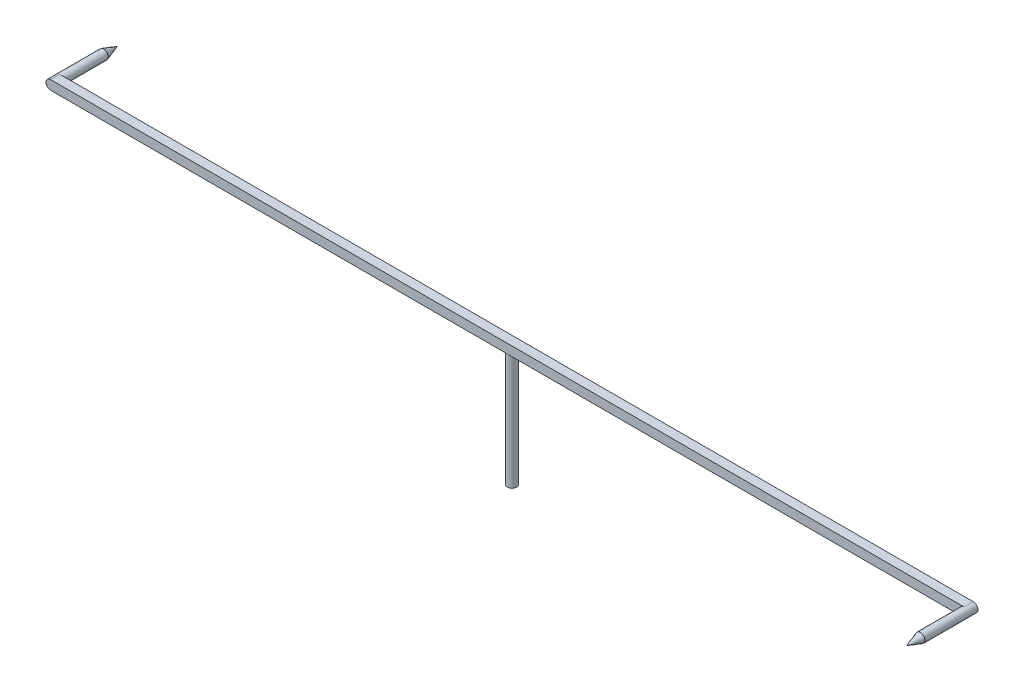
SolidWorks part; units mm, degrees
ref_plane "前视基准面" through (0, 0, 0) normal (0, 0, 1) x (1, 0, 0)
ref_plane "上视基准面" through (0, 0, 0) normal (0, 1, 0) x (1, 0, 0)
ref_plane "右视基准面" through (0, 0, 0) normal (1, 0, 0) x (0, 0, -1)
sketch "草图1" plane through (0, 0, 0) normal (0, 1, 0) x (1, 0, 0)
  circle A0 centre (0, 0) radius 0.4
  dimension "D1" = 0.8
extrude "凸台-拉伸1" add sketch "草图1" along normal blind 10
sketch "草图2" plane through (0, 10, 0) normal (0, 1, 0) x (1, 0, 0)
  line L1 (-40, 0.4) -> (40, 0.4)
  line L2 (-40, 0.4) -> (-40, -0.4)
  line L3 (-40, -0.4) -> (40, -0.4)
  line L4 (40, 0.4) -> (40, -0.4)
  circle A0 centre (0, 0) radius 0.4 construction
  dimension "D1" = 40
  dimension "D2" = 40
extrude "凸台-拉伸2" add sketch "草图2" along normal blind 0.8
fillet "圆角1" radius 0.4 4 edges at (40, 10, 0) (40, 10.8, 0) (-40, 10, 0) (-40, 10.8, 0)
sketch "草图3" plane through (0, 0, 0.4) normal (0, 0, 1) x (1, 0, 0)
  circle A0 centre (39.6, 10.4) radius 0.4
  dimension "D1" = 0.8
extrude "凸台-拉伸3" add sketch "草图3" along normal blind 3.8
sketch "草图4" plane through (0, 0, -0.4) normal (0, 0, -1) x (-1, 0, 0)
  circle A0 centre (39.6, 10.4) radius 0.4
  dimension "D1" = 0.8
extrude "凸台-拉伸4" add sketch "草图4" along normal blind 3.8
ref_plane "基准面1" through (0, 10.4, 0) normal (0, 1, 0) x (1, 0, 0)
sketch "草图5" plane through (0, 10.4, 0) normal (0, 1, 0) x (1, 0, 0)
  line L0 (39.6, -4.2) -> (39.6, -5.4)
  line L1 (39.2, -4.2) -> (40, -4.2) construction
  line L2 (40, -4.2) -> (39.6, -5.4)
  line L3 (39.6, -4.2) -> (40, -4.2)
  dimension "D1" = 1.2
revolve "旋转1" add sketch "草图5" angle 360 about L0
sketch "草图6" plane through (0, 10.4, 0) normal (0, 1, 0) x (1, 0, 0)
  line L0 (-39.6, 4.2) -> (-39.6, 5.4)
  line L1 (-39.2, 4.2) -> (-40, 4.2) construction
  line L2 (-39.6, 5.4) -> (-40, 4.2)
  line L3 (-40, 4.2) -> (-39.6, 4.2)
  dimension "D1" = 1.2
revolve "旋转2" add sketch "草图6" angle 360 about L0
